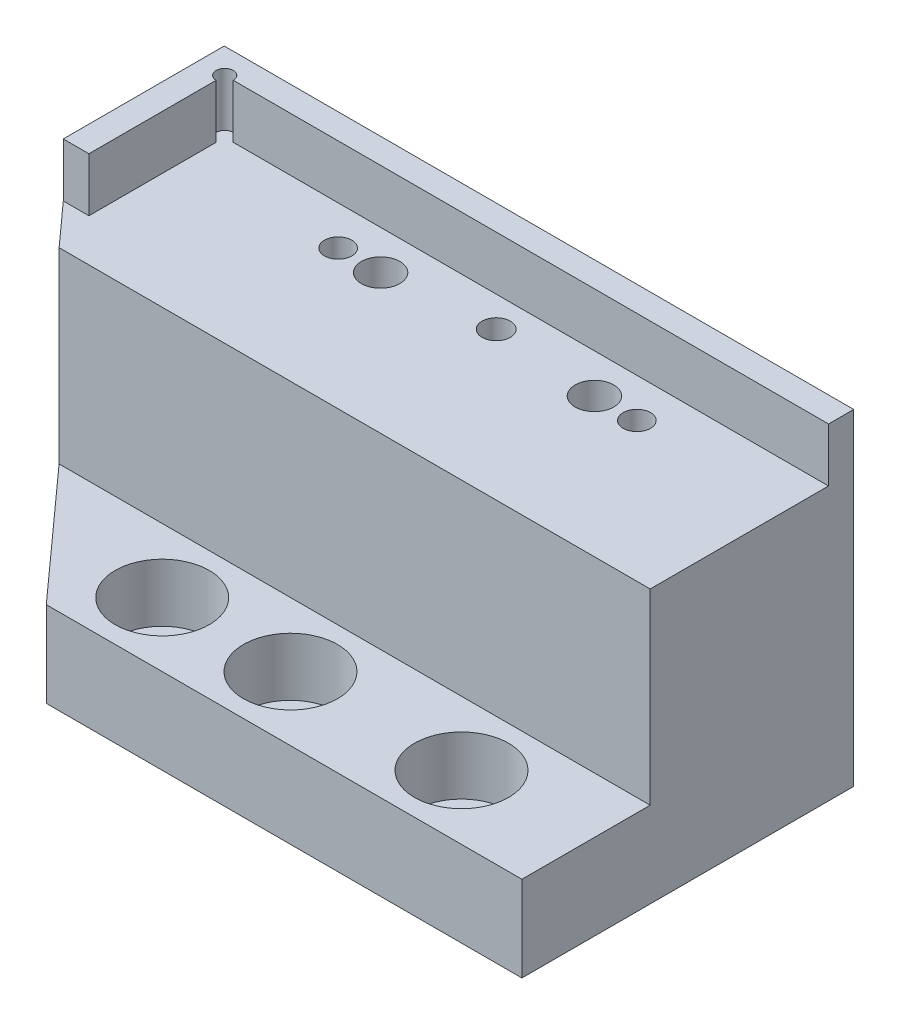
SolidWorks part; units mm, degrees
material "6061 合金"
ref_plane "前视基准面" through (0, 0, 0) normal (0, 0, 1) x (1, 0, 0)
ref_plane "上视基准面" through (0, 0, 0) normal (0, 1, 0) x (1, 0, 0)
ref_plane "右视基准面" through (0, 0, 0) normal (1, 0, 0) x (0, 0, -1)
sketch "草图1" plane through (0, 0, 0) normal (0, 1, 0) x (1, 0, 0)
  line L1 (-38.3, 11.9) -> (38.3, 11.9)
  line L2 (-38.3, 11.9) -> (-38.3, -11.9)
  line L3 (-38.3, -11.9) -> (38.3, -11.9)
  line L4 (38.3, 11.9) -> (38.3, -11.9)
  line L5 (-38.3, 11.9) -> (38.3, -11.9) construction
  line L6 (-38.3, -11.9) -> (38.3, 11.9) construction
  point P0 (0, 0)
  dimension "D1" = 76.6
  dimension "D2" = 23.8
extrude "凸台-拉伸1" add sketch "草图1" against normal up to surface (31.9 mm away)
sketch "草图2" plane through (0, 0, 0) normal (0, 1, 0) x (1, 0, 0)
  line L0 (-38.3, 5.4) -> (38.3, 5.4) construction
  line L1 (-38.3, 11.9) -> (-38.3, -11.9) construction
  line L2 (38.3, -11.9) -> (38.3, 11.9) construction
  line L3 (0, 5.4) -> (0, 11.9) construction
  line L4 (38.3, 11.9) -> (-38.3, 11.9) construction
  line L5 (0, 5.4) -> (4.9072, 5.4) construction
  line L6 (4.9072, 5.4) -> (8.8497, 5.4) construction
  line L7 (8.8497, 5.4) -> (13.7412, 5.4) construction
  line L8 (-38.3, -11.9) -> (38.3, -11.9) construction
  line L9 (-38.3, 4.384) -> (38.3, 4.384) construction
  circle A5 centre (12.5, 4.384) radius 2.027
  circle A6 centre (17.4625, 4.384) radius 1.1223
  circle A7 centre (22.225, 4.384) radius 1.0645
  circle A8 centre (12.5, 4.384) radius 1.65 construction
  circle A9 centre (17.4625, 4.384) radius 1.6002 construction
  circle A10 centre (22.225, 4.384) radius 1.7272 construction
  dimension "D1" = 17.3
hole_wizard "M4 螺纹孔1" positions "3D草图1" profile "草图3" tap size "M4" standard "GB"
sketch3d "3D草图1"
  point P0 (0, 0, -5.4)
sketch "草图3" plane through (0, 0, -5.4) normal (1, 0, 0) x (0, 0, 1)
  line L0 (0, 0) -> (0, 11.0914)
  line L1 (0, 11.0914) -> (1.65, 10.1)
  line L2 (1.65, 10.1) -> (1.65, 0)
  line L5 (1.65, 0) -> (0, 0)
  line L10 (0, 11.0914) -> (-1.65, 10.1) construction
  line L11 (0, -6.35) -> (0, 107.95) construction
  dimension "螺纹孔钻头直径" = 3.3
  dimension "螺纹孔钻头深度" = 10.1
  dimension "导头角度" = 118
cosmetic thread "孔螺蚊线1" parameters "D1"=8, "D2"=4
sketch "草图5" plane through (-38.3, 0, 0) normal (-1, 0, 0) x (0, 0, 1)
  line L1 (11.9, 0) -> (-11.9, 0)
  line L2 (11.9, 0) -> (11.9, 2.2814)
  line L3 (11.9, 2.2814) -> (-11.9, 2.2814)
  line L4 (-11.9, 0) -> (-11.9, 2.2814)
extrude "凸台-拉伸2" add sketch "草图5" against normal up to surface (2.994 mm away)
sketch "草图6" plane through (0, 0, -11.9) normal (0, 0, -1) x (-1, 0, 0)
  line L1 (-38.3, 0) -> (38.3, 0)
  line L2 (-38.3, 0) -> (-38.3, 2.2814)
  line L3 (-38.3, 2.2814) -> (38.3, 2.2814)
  line L4 (38.3, 0) -> (38.3, 2.2814)
extrude "凸台-拉伸3" add sketch "草图6" against normal up to surface (2.944 mm away)
sketch "草图7" plane through (38.3, 0, 0) normal (1, 0, 0) x (0, 0, -1)
  line L1 (11.9, -31.9) -> (-15.0921, -31.9)
  line L2 (11.9, -31.9) -> (11.9, 15.4396)
  line L3 (11.9, 15.4396) -> (-15.0921, 15.4396)
  line L4 (-15.0921, -31.9) -> (-15.0921, 15.4396)
extrude "切除-拉伸1" cut sketch "草图7" against normal up to surface (2.994 mm away)
hole_wizard "大小mm 暗销孔1" positions "草图8" profile "草图9" hole size "Ø3.0" standard "GB"
sketch "草图8" plane through (0, 0, 0) normal (0, 1, 0) x (1, 0, 0)
  point P0 (17.4625, 4.384)
sketch "草图9" plane through (17.4625, 0, -4.384) normal (1, 0, 0) x (0, 0, 1)
  line L0 (0, 0) -> (0, 5.9614)
  line L1 (0, 5.9614) -> (1.6, 5)
  line L2 (1.6, 5) -> (1.6, 0)
  line L5 (1.6, 0) -> (0, 0)
  line L10 (0, 5.9614) -> (-1.6, 5) construction
  line L11 (0, -6.35) -> (0, 107.95) construction
  dimension "孔直径" = 3.2
  dimension "孔深度" = 5
  dimension "导头角度" = 118
ref_plane "基准面4" through (0, 0, 0) normal (1, 0, 0) x (0, 0, -1)
sketch "草图10" plane through (0, 0, 11.9) normal (0, 0, 1) x (1, 0, 0)
  line L7 (35.306, -31.9) -> (-38.3, -31.9) construction
  line L8 (15, -10) -> (46.6582, -10)
  line L9 (15, -10) -> (15, -21.9)
  line L10 (15, -21.9) -> (46.6582, -21.9)
  line L11 (46.6582, -10) -> (46.6582, -21.9)
  line L12 (-35.306, 0) -> (35.306, 0) construction
  line L13 (0, -13.09) -> (0, 13.09) construction
  dimension "D1" = 10
  dimension "D2" = 10
  dimension "D3" = 15
extrude "切除-拉伸2" [suppressed] cut sketch "草图10" against normal through all
sketch "草图11" [suppressed] plane through (0, -21.9, 0) normal (0, 1, 0) x (1, 0, 0)
  line L0 (35.306, 0) -> (15, 0) construction
  line L1 (35.306, -11.9) -> (35.306, 11.9) construction
  line L2 (15, 11.9) -> (15, -11.9) construction
  line L3 (25.153, 0) -> (25.153, -11.9) construction
  line L4 (15, -11.9) -> (35.306, -11.9) construction
hole_wizard "打孔尺寸(%根据)内六角圆柱头螺钉的类型1" [suppressed] positions "3D草图2" profile "草图12" counterbore size "M6" standard "GB"
sketch3d "3D草图2" [suppressed]
  point P0 (25.153, -21.9, 0)
sketch "草图12" plane through (25.153, -21.9, 0) normal (1, 0, 0) x (0, 0, 1)
  line L0 (0, 0) -> (0, 10)
  line L1 (0, 10) -> (3.5, 10)
  line L3 (3.5, 10) -> (3.5, 6.8)
  line L4 (3.5, 6.8) -> (5.5, 6.8)
  line L5 (5.5, 6.8) -> (5.5, 0)
  line L7 (5.5, 0) -> (0, 0)
  line L11 (0, -6.35) -> (0, 107.95) construction
  dimension "通孔孔直径" = 7
  dimension "通孔孔深度" = 10
  dimension "柱形沉头孔直径" = 11
  dimension "柱形沉头孔深度" = 6.8
mirror "镜向3" about plane through (0, 0, 0) normal (1, 0, 0) of "切除-拉伸2", "打孔尺寸(%根据)内六角圆柱头螺钉的类型1", "大小mm 暗销孔1"
sketch "草图16" plane through (0, -31.9, 0) normal (0, -1, 0) x (1, 0, 0)
  line L0 (-38.3, 6.9219) -> (-55.2473, -11.9)
  line L1 (-55.2473, -11.9) -> (-38.3, -11.9)
  line L2 (-33.8177, 11.9) -> (-20.3116, 26.9)
  line L3 (-20.3116, 26.9) -> (35.306, 26.9)
  line L4 (35.306, 26.9) -> (35.306, 11.9)
  line L5 (35.306, 11.9) -> (-38.3, 11.9) construction
  line L6 (-49.6125, -5.6419) -> (-5.4498, 43.4057) construction
  line L7 (-38.3, 6.9219) -> (-38.3, -11.9)
  line L8 (-33.8177, 11.9) -> (35.306, 11.9)
  line L9 (35.306, -11.9) -> (35.306, 11.9) construction
  dimension "D1" = 15
extrude "凸台-拉伸4" add sketch "草图16" against normal blind 10
sketch "草图19" plane through (0, -21.9, 0) normal (0, 1, 0) x (1, 0, 0)
  line L0 (35.306, -19.4) -> (20.7442, -19.4) construction
  line L1 (35.306, -11.9) -> (35.306, -26.9) construction
  line L2 (20.7442, -19.4) -> (0.7442, -19.4) construction
  line L3 (0.7442, -19.4) -> (-14.2558, -19.4) construction
  line L4 (0.7442, -11.9) -> (0.7442, -19.4) construction
  line L5 (-33.8177, -11.9) -> (35.306, -11.9) construction
  line L6 (-46.7736, 11.9) -> (-46.7736, 5.9) construction
  line L7 (-55.2473, 11.9) -> (-38.3, 11.9) construction
  line L8 (-46.7736, 5.9) -> (-44.3, 5.9) construction
  line L9 (-44.3, 5.9) -> (-38.3, 5.9) construction
  line L10 (-38.3, 11.9) -> (-38.3, -6.9219) construction
  dimension "D1" = 20
  dimension "D2" = 15
  dimension "D3" = 6
hole_wizard "打孔尺寸(%根据)内六角圆柱头螺钉的类型3" positions "3D草图4" profile "草图20" counterbore size "M6" standard "GB" end condition through all
sketch3d "3D草图4"
  point P0 (-14.2558, -21.9, 19.4)
  point P3 (0.7442, -21.9, 19.4)
  point P6 (20.7442, -21.9, 19.4)
sketch "草图20" plane through (-14.2558, -21.9, 19.4) normal (1, 0, 0) x (0, 0, 1)
  line L0 (0, 0) -> (0, 10)
  line L1 (0, 10) -> (3.3, 10)
  line L3 (3.3, 10) -> (3.3, 6.8)
  line L4 (3.3, 6.8) -> (5.5, 6.8)
  line L5 (5.5, 6.8) -> (5.5, 0)
  line L7 (5.5, 0) -> (0, 0)
  line L11 (0, -6.35) -> (0, 107.95) construction
  dimension "通孔孔直径" = 6.6
  dimension "通孔孔深度" = 10
  dimension "柱形沉头孔直径" = 11
  dimension "柱形沉头孔深度" = 6.8
sketch "草图21" plane through (0, -21.9, 0) normal (0, 1, 0) x (1, 0, 0)
  circle A0 centre (-44.3, 5.9) radius 3.3
extrude "切除-拉伸6" cut sketch "草图21" against normal through all
sketch "草图22" plane through (0, -21.9, 0) normal (0, 1, 0) x (1, 0, 0)
  circle A0 centre (-44.3, 5.9) radius 5.5
sketch "草图23" plane through (0, -31.9, 0) normal (0, -1, 0) x (-1, 0, 0)
  line L0 (-0.7442, -19.4) -> (-0.7442, -9.4) construction
  line L3 (9.2558, -9.4) -> (-10.7442, -9.4) construction
  point P7 (-0.7442, -9.4)
  dimension "D1" = 10
  dimension "D2" = 20
hole_wizard "大小mm 暗销孔2" positions "3D草图5" profile "草图24" hole size "Ø4.0" standard "GB"
sketch3d "3D草图5"
  point P3 (10.7442, -31.9, 9.4)
sketch "草图24" plane through (10.7442, -31.9, 9.4) normal (1, 0, 0) x (0, 0, -1)
  line L0 (0, 0) -> (0, 6.2017)
  line L1 (0, 6.2017) -> (2, 5)
  line L2 (2, 5) -> (2, 0)
  line L5 (2, 0) -> (0, 0)
  line L10 (0, 6.2017) -> (-2, 5) construction
  line L11 (0, -6.35) -> (0, 107.95) construction
  dimension "孔直径" = 4
  dimension "孔深度" = 5
  dimension "导头角度" = 118
sketch "草图25" plane through (0, -31.9, 0) normal (0, -1, 0) x (1, 0, 0)
  line L0 (-9.7558, 9.4) -> (-8.7558, 9.4) construction
  line L1 (-9.2558, 9.4) -> (10.7442, 9.4) construction
  line L2 (-9.7558, 11.4) -> (-8.7558, 11.4)
  line L3 (-9.7558, 7.4) -> (-8.7558, 7.4)
  arc A0 (-9.7558, 11.4) -> (-9.7558, 7.4) centre (-9.7558, 9.4) ccw
  arc A1 (-8.7558, 7.4) -> (-8.7558, 11.4) centre (-8.7558, 9.4) ccw
  point P5 (-9.2558, 9.4)
  dimension "D1" = 2
  dimension "D2" = 1
extrude "切除-拉伸7" cut sketch "草图25" against normal blind 5
fillet "圆角1" [suppressed] radius 5
sketch "草图26" plane through (-24.5937, 0, 22.1443) normal (-0.7431, 0, 0.6691) x (0.6691, 0, 0.7431)
  line L0 (-35.6822, -21.9) -> (-34.027, -21.9) construction
  line L1 (-34.8546, -21.9) -> (11.1992, -21.9)
  line L2 (-34.8546, -21.9) -> (-34.8546, -31.9)
  line L3 (-34.8546, -31.9) -> (11.1992, -31.9)
  line L4 (11.1992, -21.9) -> (11.1992, -31.9)
  line L5 (14.9149, -31.9) -> (7.4835, -31.9) construction
extrude "切除-拉伸8" cut sketch "草图26" along normal through all
sketch "草图27" plane through (0, -21.9, 0) normal (0, -1, 0) x (1, 0, 0)
  line L3 (-38.3, 6.9219) -> (-33.8177, 11.9)
  line L4 (-33.8177, 11.9) -> (-38.3, 11.9)
  line L5 (-38.3, 11.9) -> (-38.3, 6.9219)
  line L6 (-38.3, 6.9219) -> (-33.8177, 11.9)
  line L7 (-33.8177, 11.9) -> (-38.3, 11.9)
  line L8 (-38.3, 11.9) -> (-38.3, 6.9219)
  dimension "D1" = 0
extrude "切除-拉伸9" cut sketch "草图27" against normal through all
ref_plane "基准面5" through (-38.3, 2.2814, -11.9) normal (-1, 0, 0) x (0, 0, 1)
sketch "草图29" plane through (0, 2.2814, 0) normal (0, 1, 0) x (1, 0, 0)
  circle A0 centre (-35.306, 8.956) radius 1
extrude "切除-拉伸10" cut sketch "草图29" against normal up to surface (2.2814 mm away) up to face at (-6.7635, 0, 3.227)
sketch "草图31" plane through (0, 2.2814, 0) normal (0, 1, 0) x (1, 0, 0)
  line L6 (-34.306, 8.956) -> (35.306, 8.956)
  line L7 (35.306, 8.956) -> (35.306, 11.9)
  line L8 (35.306, 11.9) -> (-38.3, 11.9)
  line L9 (-38.3, 11.9) -> (-38.3, -6.9219)
  line L10 (-38.3, -6.9219) -> (-35.306, -10.2471)
  line L11 (-35.306, -10.2471) -> (-35.306, 7.956)
  line L12 (-34.306, 8.956) -> (35.306, 8.956)
  line L13 (35.306, 8.956) -> (35.306, 11.9)
  line L14 (35.306, 11.9) -> (-38.3, 11.9)
  line L15 (-38.3, 11.9) -> (-38.3, -6.9219)
  line L16 (-38.3, -6.9219) -> (-35.306, -10.2471)
  line L17 (-35.306, -10.2471) -> (-35.306, 7.956)
  arc A1 (-34.306, 8.956) -> (-35.306, 7.956) centre (-35.306, 8.956) ccw
  arc A2 (-34.306, 8.956) -> (-35.306, 7.956) centre (-35.306, 8.956) ccw
  dimension "D1" = 0
extrude "凸台-拉伸5" add sketch "草图31" along normal blind 4
sketch "草图32" plane through (-24.5937, 0, 22.1443) normal (-0.7431, 0, 0.6691) x (0.6691, 0, 0.7431)
  line L10 (-20.4837, -21.9) -> (-45.8111, -21.9)
  line L11 (-45.8111, -21.9) -> (-45.8111, -31.9)
  line L12 (-45.8111, -31.9) -> (6.3995, -31.9)
  line L13 (6.3995, -31.9) -> (6.3995, -21.9)
  line L14 (6.3995, -21.9) -> (-13.785, -21.9)
  line L15 (-13.785, -21.9) -> (-13.785, 0)
  line L16 (-13.785, 0) -> (-16.0093, 0)
  line L17 (-16.0093, 0) -> (-16.0093, 6.2814)
  line L18 (-16.0093, 6.2814) -> (-20.4837, 6.2814)
  line L19 (-20.4837, 6.2814) -> (-20.4837, -21.9)
  line L20 (-23.8135, -21.9) -> (-45.8111, -21.9)
  line L21 (-45.8111, -21.9) -> (-45.8111, -31.9)
  line L22 (-45.8111, -31.9) -> (7.4987, -31.9)
  line L23 (7.4987, -31.9) -> (7.4987, -21.9)
  line L24 (7.4987, -21.9) -> (-11.9518, -21.9)
  line L25 (-11.9518, -21.9) -> (-11.9518, 0)
  line L26 (-11.9518, 0) -> (-16.0093, 0)
  line L27 (-16.0093, 0) -> (-16.0093, 6.2814)
  line L28 (-16.0093, 6.2814) -> (-23.8135, 6.2814)
  line L29 (-23.8135, 6.2814) -> (-23.8135, -21.9)
  dimension "D1" = 0
extrude "切除-拉伸11" cut sketch "草图32" against normal blind 0.5
sketch "草图33" plane through (-24.2221, 0, 21.8097) normal (-0.7431, 0, 0.6691) x (0.6691, 0, 0.7431)
  line L10 (-45.3609, -21.9) -> (-45.3609, -31.9)
  line L11 (-45.3609, -31.9) -> (6.8497, -31.9)
  line L12 (6.8497, -31.9) -> (6.8497, -21.9)
  line L13 (6.8497, -21.9) -> (-13.3348, -21.9)
  line L14 (-13.3348, -21.9) -> (-13.3348, 0)
  line L15 (-13.3348, 0) -> (-16.5646, 0)
  line L16 (-16.5646, 0) -> (-16.5646, 6.2814)
  line L17 (-16.5646, 6.2814) -> (-21.039, 6.2814)
  line L18 (-21.039, 6.2814) -> (-21.039, -21.9)
  line L19 (-21.039, -21.9) -> (-45.3609, -21.9)
  line L20 (-45.3609, -21.9) -> (-45.3609, -31.9)
  line L21 (-45.3609, -31.9) -> (6.8497, -31.9)
  line L22 (6.8497, -31.9) -> (6.8497, -21.9)
  line L23 (6.8497, -21.9) -> (-13.3348, -21.9)
  line L24 (-13.3348, -21.9) -> (-13.3348, 0)
  line L25 (-13.3348, 0) -> (-16.5646, 0)
  line L26 (-16.5646, 0) -> (-16.5646, 6.2814)
  line L27 (-16.5646, 6.2814) -> (-21.039, 6.2814)
  line L28 (-21.039, 6.2814) -> (-21.039, -21.9)
  line L29 (-21.039, -21.9) -> (-45.3609, -21.9)
  dimension "D1" = 0
extrude "凸台-拉伸6" add sketch "草图33" along normal up to surface (0.5 mm away)
sketch "草图34" plane through (0, 6.2814, 0) normal (0, 1, 0) x (1, 0, 0)
  line L0 (-38.3, -6.1746) -> (-38.3, -6.9219)
  line L1 (-35.6776, -9.8344) -> (-38.6716, -6.5092) construction
  line L2 (-33.1449, -11.9) -> (-33.8177, -11.9)
  line L3 (-33.5164, -12.2346) -> (-35.6776, -9.8344) construction
  line L4 (-33.8177, -11.9) -> (-33.5164, -12.2346)
  line L5 (-33.5164, -12.2346) -> (-33.1449, -11.9)
  line L6 (-38.3, -6.1746) -> (-38.6716, -6.5092)
  line L7 (-38.6716, -6.5092) -> (-38.3, -6.9219)
extrude "切除-拉伸12" cut sketch "草图34" against normal up to surface (28.1814 mm away) up to face at (-47.6, -21.9, -5.9)
sketch "草图35" plane through (35.306, 0, 0) normal (1, 0, 0) x (0, 0, -1)
  line L4 (-27.2346, -21.9) -> (-27.2346, -31.9)
  line L5 (-27.2346, -31.9) -> (-26.9, -31.9)
  line L6 (-26.9, -31.9) -> (-26.9, -21.9)
  line L7 (-26.9, -21.9) -> (-27.2346, -21.9)
  line L8 (-27.2346, -21.9) -> (-27.2346, -31.9)
  line L9 (-27.2346, -31.9) -> (-26.9, -31.9)
  line L10 (-26.9, -31.9) -> (-26.9, -21.9)
  line L11 (-26.9, -21.9) -> (-27.2346, -21.9)
  dimension "D1" = 0
extrude "切除-拉伸13" cut sketch "草图35" against normal through all
chamfer "倒角1" distance 2 angle 45 2 edges at (-54.946, -26.9, -11.5654) (-35.6776, 3.1407, 9.8344)
sketch "草图36" plane through (0, -31.9, 0) normal (0, -1, 0) x (-1, 0, 0)
  line L2 (9.7558, -7.4) -> (8.7558, -7.4)
  line L3 (8.7558, -11.4) -> (9.7558, -11.4)
  line L4 (9.7558, -7.4) -> (8.7558, -7.4)
  line L5 (8.7558, -11.4) -> (9.7558, -11.4)
  circle A0 centre (-10.7442, -9.4) radius 2
  circle A1 centre (9.2558, -9.4) radius 2
  arc A4 (9.7558, -11.4) -> (9.7558, -7.4) centre (9.7558, -9.4) ccw
  arc A5 (8.7558, -7.4) -> (8.7558, -11.4) centre (8.7558, -9.4) ccw
  arc A6 (9.7558, -11.4) -> (9.7558, -7.4) centre (9.7558, -9.4) ccw
  arc A7 (8.7558, -7.4) -> (8.7558, -11.4) centre (8.7558, -9.4) ccw
  dimension "D1" = 0
hole_wizard "打孔尺寸(%根据)内六角圆柱头螺钉的类型4" positions "3D草图7" profile "草图38" counterbore size "M4" standard "GB" end condition through all
sketch3d "3D草图7"
  circle A0 centre (12.5, 0, -4.384) radius 2.027 construction
  point P0 (12.5, -31.9, -4.384)
  point P6 (12.5, 2.027, -4.384)
sketch "草图38" plane through (12.5, -31.9, -4.384) normal (1, 0, 0) x (0, 0, -1)
  line L0 (0, 0) -> (0, 38.1814)
  line L1 (0, 38.1814) -> (2.25, 38.1814)
  line L3 (2.25, 38.1814) -> (2.25, 25)
  line L4 (2.25, 25) -> (4, 25)
  line L5 (4, 25) -> (4, 0)
  line L7 (4, 0) -> (0, 0)
  line L11 (0, -6.35) -> (0, 107.95) construction
  dimension "通孔孔直径" = 4.5
  dimension "通孔孔深度" = 38.1814
  dimension "柱形沉头孔直径" = 8
  dimension "柱形沉头孔深度" = 25
mirror "镜向4" about plane through (0, 0, 0) normal (1, 0, 0) of "打孔尺寸(%根据)内六角圆柱头螺钉的类型4"
sketch "草图39" plane through (0, -21.9, 0) normal (0, 1, 0) x (1, 0, 0)
  line L0 (-53.5124, 11.9) -> (-53.5124, 9.9732)
  line L1 (-38.3, -6.9219) -> (-53.6078, 10.0792) construction
  line L2 (-53.5124, 9.9732) -> (-53.6078, 10.0792)
  line L3 (-53.6078, 10.0792) -> (-53.5124, 11.9)
extrude "切除-拉伸14" cut sketch "草图39" against normal through all
sketch "草图40" plane through (0, 6.2814, 0) normal (0, 1, 0) x (1, 0, 0)
  line L0 (-38.3, -6.9219) -> (-35.306, -6.9219)
  line L1 (-37.0158, -8.3481) -> (-38.3, -6.9219) construction
  line L2 (-35.306, -8.4377) -> (-35.306, 7.956) construction
  line L3 (-38.3, -6.9219) -> (-37.0158, -8.3481)
  line L4 (-37.0158, -8.3481) -> (-35.306, -8.4377)
  line L5 (-35.306, -8.4377) -> (-35.306, -6.9219)
extrude "切除-拉伸15" cut sketch "草图40" against normal up to surface (6.2814 mm away) up to face at (-12.5, 0, -2.134)
sketch "草图41" plane through (0, 0, 6.9219) normal (0, 0, 1) x (1, 0, 0)
  line L4 (-38.3, 0) -> (-35.306, 0)
  line L5 (-35.306, 0) -> (-35.306, 6.2814)
  line L6 (-35.306, 6.2814) -> (-38.3, 6.2814)
  line L7 (-38.3, 6.2814) -> (-38.3, 0)
  line L8 (-38.3, 0) -> (-35.306, 0)
  line L9 (-35.306, 0) -> (-35.306, 6.2814)
  line L10 (-35.306, 6.2814) -> (-38.3, 6.2814)
  line L11 (-38.3, 6.2814) -> (-38.3, 0)
  dimension "D1" = 0
extrude "凸台-拉伸7" [suppressed] add sketch "草图41" along normal up to surface (3.3252 mm away)
sketch "草图42" plane through (-38.3, 0, 0) normal (-1, 0, 0) x (0, 0, 1)
  line L5 (-11.9, -21.9) -> (6.9219, -21.9)
  line L6 (6.9219, -21.9) -> (6.9219, 0)
  line L7 (6.9219, 0) -> (6.9219, 6.2814)
  line L8 (6.9219, 6.2814) -> (-11.9, 6.2814)
  line L9 (-11.9, 6.2814) -> (-11.9, -21.9)
  line L10 (-11.9, -21.9) -> (6.9219, -21.9)
  line L11 (6.9219, -21.9) -> (6.9219, 0)
  line L12 (6.9219, 0) -> (6.9219, 6.2814)
  line L13 (6.9219, 6.2814) -> (-11.9, 6.2814)
  line L14 (-11.9, 6.2814) -> (-11.9, -21.9)
  dimension "D1" = 0
extrude "凸台-拉伸9" add sketch "草图42" along normal offset from surface (0.006 mm away) 3 up to face at (-35.306, 3.1407, -0.5171)
